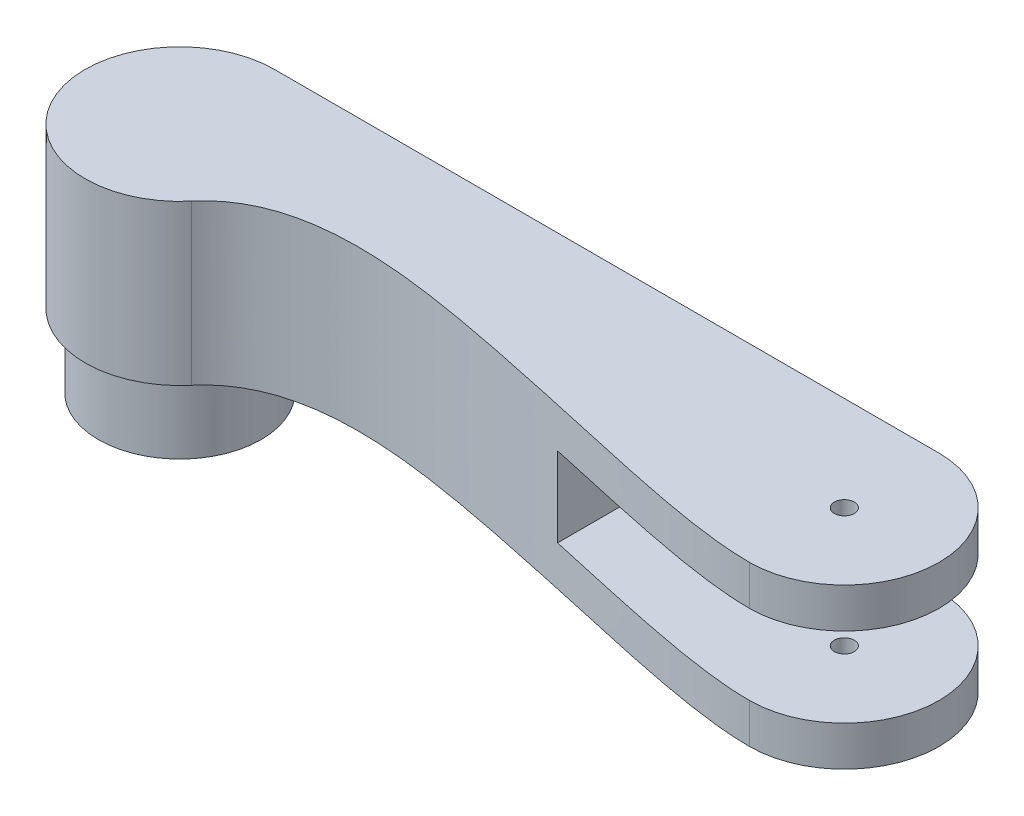
SolidWorks part; units mm, degrees
ref_plane "Front Plane" through (0, 0, 0) normal (0, 0, 1) x (1, 0, 0)
ref_plane "Top Plane" through (0, 0, 0) normal (0, 1, 0) x (1, 0, 0)
ref_plane "Right Plane" through (0, 0, 0) normal (1, 0, 0) x (0, 0, -1)
sketch "Sketch1" plane through (0, 0, 0) normal (0, 1, 0) x (1, 0, 0)
  line L0 (-50, 0) -> (50, 0) construction
  line L1 (-50, 14.25) -> (50, 14.25)
  line L2 (-50, -14.25) -> (50, -14.25)
  arc A0 (-50, 14.25) -> (-50, -14.25) centre (-50, 0) ccw
  arc A1 (50, -14.25) -> (50, 14.25) centre (50, 0) ccw
  point P3 (0, 0)
  dimension "D1" = 14.25
  dimension "D2" = 100
extrude "Boss-Extrude1" add sketch "Sketch1" along normal blind 6
sketch "Sketch3" plane through (0, 0, 0) normal (0, -1, 0) x (1, 0, 0)
  circle A0 centre (50, 0) radius 1.5
  dimension "D1" = 3
extrude "Cut-Extrude2" cut sketch "Sketch3" against normal through all
sketch "Sketch4" plane through (0, 6, 0) normal (0, 1, 0) x (1, 0, 0)
  line L0 (-50, 14.25) -> (15, 14.25)
  line L1 (-50, 14.25) -> (50, 14.25) construction
  line L2 (15, 14.25) -> (15, -14.25)
  line L3 (-50, -14.25) -> (50, -14.25) construction
  line L4 (15, -14.25) -> (-50, -14.25)
  arc A0 (-50, 14.25) -> (-50, -14.25) centre (-50, 0) ccw
  arc A1 (-50, 14.25) -> (-50, -14.25) centre (-50, 0) ccw construction
  dimension "D1" = 65
extrude "Boss-Extrude2" add sketch "Sketch4" along normal blind 12
sketch "Sketch5" plane through (0, 18, 0) normal (0, 1, 0) x (1, 0, 0)
  line L0 (-50, 0) -> (50, 0) construction
  line L1 (-50, 14.25) -> (50, 14.25)
  line L2 (-50, -14.25) -> (50, -14.25)
  arc A0 (-50, 14.25) -> (-50, -14.25) centre (-50, 0) ccw
  arc A1 (50, -14.25) -> (50, 14.25) centre (50, 0) ccw
  point P4 (0, 0)
  dimension "D1" = 14.25
extrude "Boss-Extrude3" add sketch "Sketch5" along normal blind 6
sketch "Sketch6" plane through (0, 24, 0) normal (0, 1, 0) x (1, 0, 0)
  circle A0 centre (50, 0) radius 1.5
  dimension "D1" = 3
extrude "Cut-Extrude3" cut sketch "Sketch6" against normal up to next
sketch "Sketch7" plane through (0, 24, 0) normal (0, 1, 0) x (1, 0, 0)
  line L0 (0, -13.2) -> (0, 13.2) construction
  line L1 (-50, -14.25) -> (50, -14.25)
  circle A0 centre (-50, 0) radius 14.25
  circle A1 centre (50, 0) radius 14.25
  spline S0 degree 3 poles (-39.0732, -9.1469) (-31.5141, -0.117) (5.4387, -4.6452) (38.6975, -14.25) (50, -14.25) knots 0 0 0 0 0.435908 1 1 1 1
  line M5 (-50, -14.25) -> (50, -14.25)
extrude "Cut-Extrude4" cut sketch "Sketch7" against normal up to next contours S0 A0 M5 region at (-8.5907, 24, 9.7914)
sketch "Sketch8" plane through (0, 0, 0) normal (0, -1, 0) x (1, 0, 0)
  circle A1 centre (-50, 0) radius 12.25
  dimension "D1" = 24.5
extrude "Boss-Extrude4" add sketch "Sketch8" along normal blind 11
sketch "Sketch9" plane through (0, -11, 0) normal (0, -1, 0) x (1, 0, 0)
  circle A0 centre (-50, 0) radius 8.25 construction
  circle A1 centre (-50, 8.25) radius 2.5
  circle A2 centre (-50, -8.25) radius 2.5
  arc A3 (-50, 14.25) -> (-50, -14.25) centre (-50, 0) ccw construction
  point P6 (-50, 0)
  dimension "D1" = 16.5
  dimension "D2" = 5
extrude "Cut-Extrude5" cut sketch "Sketch9" against normal blind 6
equation "\"Length\"= 100mm"
equation "\"Radius\"= 14.25mm"
equation "\"Thick\"= 12mm"
equation "\"D1@Sketch1\"= \"Radius\""
equation "\"D2@Sketch1\" = \"Length\""
equation "\"D1@Boss-Extrude1\"= \"Thick\""
equation "\"D1@Sketch4\"=\"Length\"*0.65"
equation "\"D1@Sketch5\"=\"Radius\""
equation "\"D1@Boss-Extrude2\"=\"Thick\""
equation "\"D1@Boss-Extrude4\"=\"Thick\"-1"
